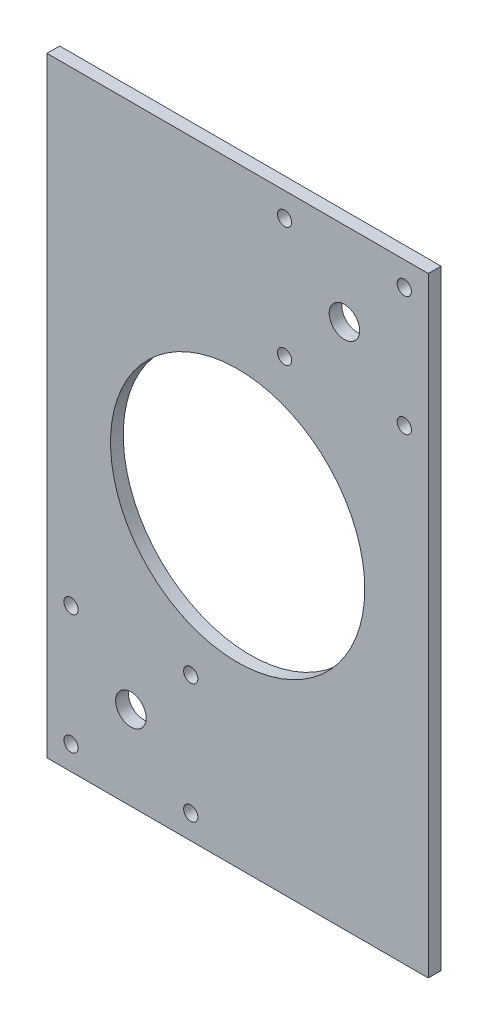
SolidWorks part; units mm, degrees
material "Mahogany"
ref_plane "Front Plane" through (0, 0, 0) normal (0, 0, 1) x (1, 0, 0)
ref_plane "Top Plane" through (0, 0, 0) normal (0, 1, 0) x (1, 0, 0)
ref_plane "Right Plane" through (0, 0, 0) normal (1, 0, 0) x (0, 0, -1)
sketch "Sketch1" plane through (0, 0, 0) normal (0, 0, 1) x (1, 0, 0)
  line L1 (-75, -120) -> (75, -120)
  line L2 (-75, -120) -> (-75, 120)
  line L3 (-75, 120) -> (75, 120)
  line L4 (75, -120) -> (75, 120)
  line L5 (-75, -120) -> (75, 120) construction
  line L6 (-75, 120) -> (75, -120) construction
  point P0 (0, 0)
  dimension "D1" = 150
  dimension "D2" = 240
extrude "Boss-Extrude1" add sketch "Sketch1" along normal blind 5
sketch "Sketch2" [suppressed] plane through (0, 0, 0) normal (0, 0, -1) x (-1, 0, 0)
  line L0 (61, 200) -> (61, -200) construction
  line L1 (-61, 314.7216) -> (-204.3993, 314.7216)
  line L2 (-61, 314.7216) -> (-61, -251.9618)
  line L3 (-61, -251.9618) -> (-204.3993, -251.9618)
  line L4 (-204.3993, 314.7216) -> (-204.3993, -251.9618)
  line L6 (61, 279.3211) -> (244.4765, 279.3211)
  line L7 (61, 279.3211) -> (61, -295.1839)
  line L8 (61, -295.1839) -> (244.4765, -295.1839)
  line L9 (244.4765, 279.3211) -> (244.4765, -295.1839)
  line L10 (-61, -200) -> (-61, -140) construction
extrude "Cut-Extrude1" [suppressed] cut sketch "Sketch2" against normal through all
sketch "Sketch3" [suppressed] plane through (49, 0, 0) normal (1, 0, 0) x (0, 0, -1)
  circle A0 centre (-6.722, 55.3681) radius 5.3835
surface "Surface-Extrude1" [suppressed] sketch "Sketch3"
sketch "Sketch4" [suppressed] plane through (-49, 0, 0) normal (-1, 0, 0) x (0, 0, 1)
  line L1 (2, 80) -> (0, 80) construction
  line L2 (0, -80) -> (0, 80) construction
  point P0 (7.5, 76)
  dimension "D1" = 4
  dimension "D2" = 7.5
ref_axis "Axis1" [suppressed] through (-49, 76, 7.5) along (1, 0, 0)
sketch "Sketch5" [suppressed] plane through (0, 0, 0) normal (0, 0, -1) x (-1, 0, 0)
  line L0 (49, 80) -> (49, -80) construction
  line L1 (-49, 80) -> (49, 80)
  line L2 (-49, 80) -> (-49, 60.2594)
  line L3 (-49, 60.2594) -> (49, 60.2594)
  line L4 (49, 80) -> (49, 60.2594)
extrude "Cut-Extrude2" [suppressed] cut sketch "Sketch5" against normal blind 3
sketch "Sketch6" [suppressed] plane through (0, 0, 2) normal (0, 0, 1) x (1, 0, 0)
  line L0 (0, 0) -> (103.2002, 0) construction
  line L1 (0, 82.0129) -> (0, 105.8319) construction
  line L2 (0, 82.0129) -> (-20.8963, 82.0129) construction
  circle A0 centre (0, 82.0129) radius 5
  circle A1 centre (0, -82.0129) radius 5
  circle A2 centre (-11.3212, 93.334) radius 1.5
  circle A3 centre (-11.3212, 70.6917) radius 1.5
  circle A4 centre (11.3212, 70.6917) radius 1.5
  circle A5 centre (11.3212, 93.334) radius 1.5
  circle A6 centre (-11.3212, -70.6917) radius 1.5
  circle A7 centre (11.3212, -70.6917) radius 1.5
  circle A8 centre (11.3212, -93.334) radius 1.5
  circle A9 centre (-11.3212, -93.334) radius 1.5
  dimension "D1" = 10
  dimension "D3" = 3
  dimension "D2" = 164.0257
extrude "Cut-Extrude3" [suppressed] cut sketch "Sketch6" against normal through all
sketch "Sketch7" plane through (0, 0, 5) normal (0, 0, 1) x (1, 0, 0)
  line L0 (0, 0) -> (0, 68.4211) construction
  line L1 (44.1624, 0) -> (-44.1624, 0) construction
  circle A0 centre (-65.55, -110.55) radius 2.8 construction
  circle A1 centre (-65.55, -63.45) radius 2.8 construction
  circle A2 centre (-18.45, -63.45) radius 2.8 construction
  circle A3 centre (-18.45, -110.55) radius 2.8 construction
  circle A4 centre (-65.55, -110.55) radius 2.8
  circle A5 centre (-65.55, -63.45) radius 2.8
  circle A6 centre (-18.45, -63.45) radius 2.8
  circle A7 centre (-18.45, -110.55) radius 2.8
  circle A8 centre (-18.45, 110.55) radius 2.8
  circle A9 centre (-18.45, 63.45) radius 2.8
  circle A10 centre (-65.55, 63.45) radius 2.8
  circle A11 centre (-65.55, 110.55) radius 2.8
  circle A12 centre (65.55, 110.55) radius 2.8
  circle A13 centre (65.55, 63.45) radius 2.8
  circle A14 centre (18.45, 63.45) radius 2.8
  circle A15 centre (18.45, 110.55) radius 2.8
  circle A16 centre (18.45, -110.55) radius 2.8
  circle A17 centre (18.45, -63.45) radius 2.8
  circle A18 centre (65.55, -63.45) radius 2.8
  circle A19 centre (65.55, -110.55) radius 2.8
  circle A20 centre (-42, -87) radius 6
  circle A21 centre (-42, 87) radius 6
  circle A22 centre (42, 87) radius 6
  circle A23 centre (42, -87) radius 6
  point P43 (0, 0)
  dimension "D1" = 12
extrude "Cut-Extrude4" cut sketch "Sketch7" against normal through all
sketch "Sketch8" plane through (0, 0, 5) normal (0, 0, 1) x (1, 0, 0)
  circle A0 centre (0, 0) radius 50
  dimension "D1" = 100
extrude "Cut-Extrude5" cut sketch "Sketch8" against normal through all
other "DeleteFace1" face at (-68.35, 110.55, 0) face at (-68.35, 63.45, 0) face at (-21.25, 63.45, 0) face at (-21.25, 110.55, 0) face at (-48, 87, 0) face at (15.65, -110.55, 0) face at (36, -87, 0) face at (15.65, -63.45, 0) face at (62.75, -63.45, 0) face at (62.75, -110.55, 0) and patch yes
